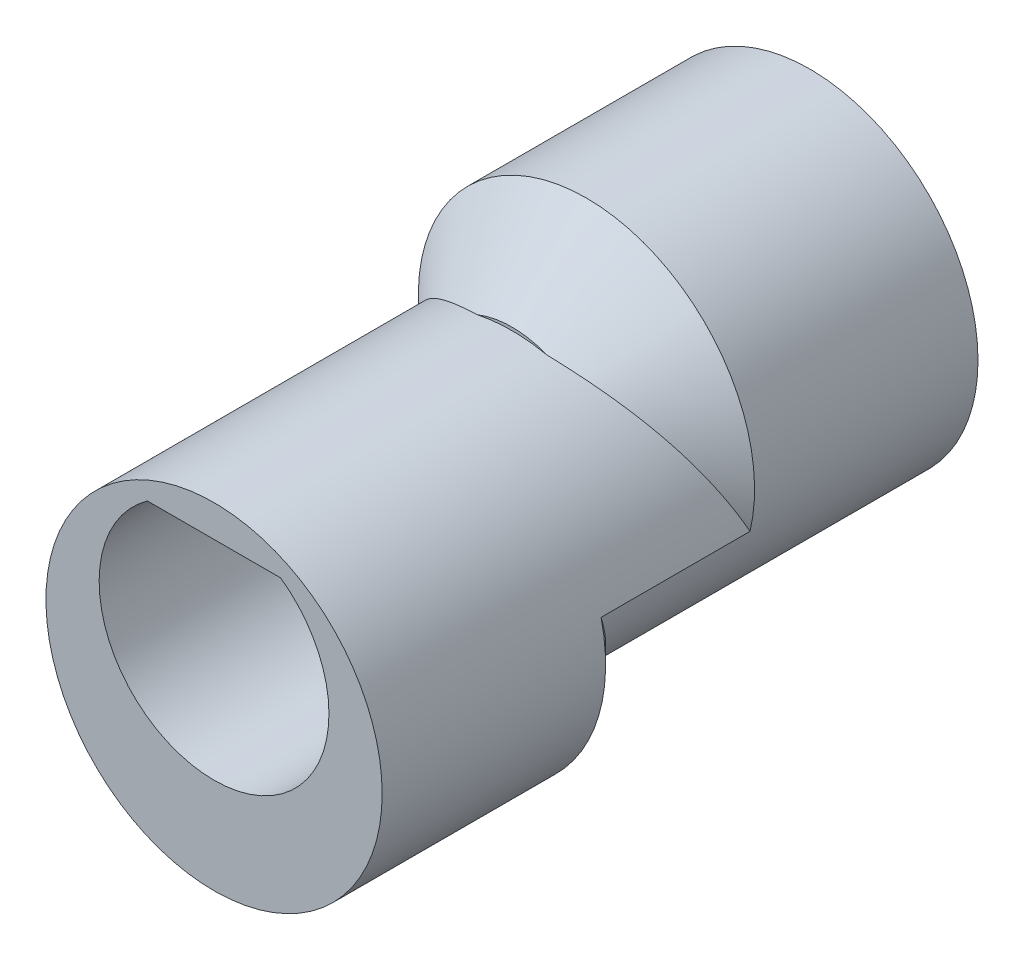
SolidWorks part; units mm, degrees
ref_plane "Plan de face" through (0, 0, 0) normal (0, 0, 1) x (1, 0, 0)
ref_plane "Plan de dessus" through (0, 0, 0) normal (0, 1, 0) x (1, 0, 0)
ref_plane "Plan de droite" through (0, 0, 0) normal (1, 0, 0) x (0, 0, -1)
sketch "Esquisse1" plane through (0, 0, 0) normal (0, 0, 1) x (1, 0, 0)
  circle A1 centre (0, 0.8221) radius 3.95
  dimension "D3" = 7.9
extrude "Boss.-Extru.1" add sketch "Esquisse1" along normal blind 7
sketch "Esquisse2" plane through (0, 0, 7) normal (0, 0, 1) x (1, 0, 0)
  circle A0 centre (0, -1) radius 3.95
  dimension "D1" = 7.9
  dimension "D2" = 1
extrude "Boss.-Extru.2" add sketch "Esquisse2" along normal blind 7
sketch "Esquisse3" plane through (0, 0, 14) normal (0, 0, 1) x (1, 0, 0)
  line L0 (-1.5, 2) -> (1.5, 2) construction
  line L1 (-1.5652, 2.2) -> (1.5652, 2.2)
  arc A0 (-1.5, 2) -> (1.5, 2) centre (0, 0) ccw construction
  arc A1 (-1.5652, 2.2) -> (1.5652, 2.2) centre (0, 0) ccw
  dimension "D1" = 5
  dimension "D2" = 2
  dimension "D3" = 0.2
extrude "Enlèv. mat.-Extru.1" cut sketch "Esquisse3" against normal through all
chamfer "Chanfrein2" distance 1.75 angle 45 1 edges at (0, 4.7721, 7)
chamfer "Chanfrein4" distance 1.75 angle 45 1 edges at (0, -4.95, 7)
